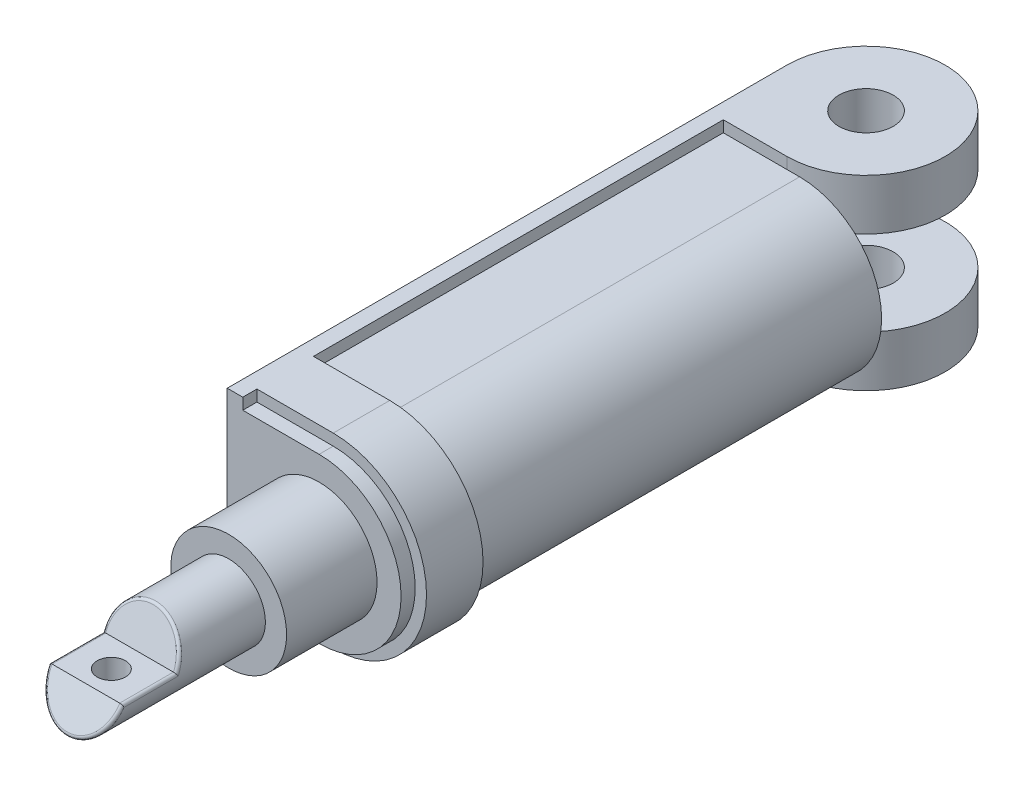
SolidWorks part; units mm, degrees
ref_plane "前视基准面" through (0, 0, 0) normal (0, 0, 1) x (1, 0, 0)
ref_plane "上视基准面" through (0, 0, 0) normal (0, 1, 0) x (1, 0, 0)
ref_plane "右视基准面" through (0, 0, 0) normal (1, 0, 0) x (0, 0, -1)
sketch "正视图" plane through (0, 0, 0) normal (0, 0, 1) x (1, 0, 0)
  line L0 (55.75, 273.25) -> (861.75, 273.25) construction
sketch "侧视图" plane through (0, 0, 0) normal (1, 0, 0) x (0, 0, -1)
  line L0 (-836.625, 271.75) -> (-66.625, 271.75) construction
sketch "上视图" plane through (0, 0, 0) normal (0, 1, 0) x (1, 0, 0)
  line L0 (71.77, 312.1) -> (815.77, 312.1) construction
ref_plane "基准面4" through (0, -30, 0) normal (0, 1, 0) x (1, 0, 0)
sketch "底视图" plane through (0, -30, 0) normal (0, 1, 0) x (1, 0, 0)
  line L0 (70.244, -367.6) -> (840.244, -367.6) construction
sketch "参考图" plane through (0, 0, 0) normal (0, 0, 1) x (1, 0, 0)
  line L0 (-599.619, 219.445) -> (198.381, 219.445) construction
  line L1 (199.5, 455.5) -> (997.5, 455.5) construction
  line L2 (-127.8038, 216.7504) -> (640.1962, 216.7504) construction
  line L3 (-679.1119, 349.8974) -> (-315.1119, 349.8974) construction
ref_plane "基准面5" through (0, -50.5, 0) normal (0, 1, 0) x (1, 0, 0)
sketch "草图1" plane through (0, -50.5, 0) normal (0, 1, 0) x (1, 0, 0)
  line L0 (65.375, 17.125) -> (65.375, 10.125)
  line L1 (65.375, 10.125) -> (58.375, 10.125)
  circle A0 centre (58.375, 17.125) radius 2.4
  circle A1 centre (58.375, 17.125) radius 7
  dimension "D3" = 4.8
  dimension "D4" = 14
  dimension "D1" = 17.125
  dimension "D2" = 58.375
extrude "凸台-拉伸1" add sketch "草图1" along normal blind 16.5 contours A1 A0 | A1 L1 L0 region at (63.1847, -50.5, -12.3153) region at (63.8114, -50.5, -11.6886)
sketch "草图2" plane through (0, 0, -10.125) normal (0, 0, 1) x (1, 0, 0)
  line L0 (73.5, -42.25) -> (57.25, -42.25) construction
  line L4 (65.375, -34) -> (65.375, -50.5) construction
  line L7 (73.5, -50.5) -> (57.25, -50.5)
  line L8 (73.5, -34) -> (57.25, -34)
  line L9 (70.75, -42.25) -> (57.25, -42.25) construction
  line L10 (70.75, -49.5) -> (57.25, -49.5)
  line L11 (70.75, -35) -> (57.25, -35)
  line L12 (60.775, -34) -> (55.975, -34) construction
  line L13 (65.375, -50.5) -> (58.375, -50.5) construction
  line L14 (65.375, -34) -> (65.375, -50.5)
  line L15 (64, -34) -> (64, -50.5)
  arc A4 (73.5, -50.5) -> (73.5, -34) centre (73.5, -42.25) ccw
  arc A5 (57.25, -34) -> (57.25, -50.5) centre (57.25, -42.25) ccw
  arc A6 (70.75, -49.5) -> (70.75, -35) centre (70.75, -42.25) ccw
  arc A7 (57.25, -35) -> (57.25, -49.5) centre (57.25, -42.25) ccw
  point P4 (65.375, -42.25)
  point P11 (64, -42.25)
  line M10 (65.375, -50.5) -> (65.375, -34)
  line M11 (65.375, -34) -> (58.375, -34)
  line M12 (58.375, -34) -> (58.375, -50.5)
  dimension "D1" = 16.25
  dimension "D2" = 1.375
  dimension "D3" = 14.5
extrude "凸台-拉伸2" add sketch "草图2" along normal blind 42.5 contours L11 A7 L10 M12 | L15 L11 L10 M12 | L15 L11 M11 M10 | L11 L15 L10 M10 | L10 L15 L7 M10 region at (64.6875, -50, -10.125) region at (64.6875, -42.25, -10.125) region at (64.6875, -34.5, -10.125) region at (61.1875, -42.25, -10.125) region at (54.7734, -42.25, -10.125)
sketch "草图3" plane through (0, 0, 32.375) normal (0, 0, 1) x (1, 0, 0)
  line L0 (64, -34) -> (64, -50.5) construction
  line L1 (65.375, -34) -> (65.375, -50.5) construction
  line L2 (57.25, -49.5) -> (70.75, -49.5)
  line L3 (70.75, -35) -> (57.25, -35)
  line L4 (57.25, -49.5) -> (70.75, -49.5)
  line L5 (70.75, -35) -> (57.25, -35)
  line L6 (57.25, -50.5) -> (73.5, -50.5)
  line L7 (73.5, -34) -> (57.25, -34)
  line L8 (57.25, -50.5) -> (73.5, -50.5)
  line L9 (73.5, -34) -> (57.25, -34)
  line L10 (64, -34) -> (64, -50.5)
  line L11 (65.375, -34) -> (65.375, -50.5)
  arc A2 (57.25, -35) -> (57.25, -49.5) centre (57.25, -42.25) ccw
  arc A3 (70.75, -49.5) -> (70.75, -35) centre (70.75, -42.25) ccw
  arc A4 (57.25, -35) -> (57.25, -49.5) centre (57.25, -42.25) ccw
  arc A5 (70.75, -49.5) -> (70.75, -35) centre (70.75, -42.25) ccw
  arc A6 (57.25, -34) -> (57.25, -50.5) centre (57.25, -42.25) ccw
  arc A7 (73.5, -50.5) -> (73.5, -34) centre (73.5, -42.25) ccw
  arc A8 (57.25, -34) -> (57.25, -50.5) centre (57.25, -42.25) ccw
  arc A9 (73.5, -50.5) -> (73.5, -34) centre (73.5, -42.25) ccw
  line M9 (64, -35) -> (57.25, -35)
  arc M10 (57.25, -35) -> (57.25, -49.5) centre (57.25, -42.25) ccw
  line M11 (57.25, -49.5) -> (64, -49.5)
  line M12 (64, -49.5) -> (64, -50.5)
  line M13 (64, -50.5) -> (65.375, -50.5)
  line M14 (65.375, -50.5) -> (65.375, -34)
  line M15 (65.375, -34) -> (64, -34)
  line M16 (64, -34) -> (64, -35)
  dimension "D1" = 0
  dimension "D2" = 0
extrude "凸台-拉伸3" add sketch "草图3" against normal blind 5 from offset 1.25 contours L9 A8 L8 M12 M11 M10 M9 M16 | L5 M14 M15 M16 | L4 M12 M13 M14 region at (60.625, -49.723, 32.375) region at (64.6875, -50, 32.375) region at (64.6875, -34.5, 32.375) offset against normal yes
ref_plane "基准面6" through (0, -42.25, 0) normal (0, 1, 0) x (1, 0, 0)
sketch "草图5" plane through (0, -42.25, 0) normal (0, 1, 0) x (1, 0, 0)
  line L1 (57.25, -32.375) -> (62.375, -32.375)
  line L2 (57.25, -32.375) -> (57.25, -40.375)
  line L3 (57.25, -40.375) -> (62.375, -40.375)
  line L4 (62.375, -32.375) -> (62.375, -40.375)
  line L5 (57.25, -40.375) -> (60.5, -40.375)
  line L6 (57.25, -40.375) -> (57.25, -54.875)
  line L7 (57.25, -54.875) -> (60.5, -54.875)
  line L8 (60.5, -40.375) -> (60.5, -54.875)
  dimension "D1" = 8
  dimension "D2" = 5.125
  dimension "D3" = 14.5
  dimension "D4" = 3.25
revolve "旋转1" add sketch "草图5" angle 360 about L2 region at (59.8125, -42.25, 36.375) region at (58.875, -42.25, 47.625)
sketch "草图6" plane through (0, 0, 0) normal (1, 0, 0) x (0, 0, -1)
  line L0 (-47, -39) -> (-48.25, -42.25)
  line L1 (-40.375, -39) -> (-54.875, -39) construction
  line L2 (-48.25, -42.25) -> (-53, -42.25)
  line L3 (-53, -42.25) -> (-54.875, -45.5)
  line L4 (-54.875, -45.5) -> (-54.875, -39)
  line L5 (-54.875, -39) -> (-54.875, -45.5) construction
  line L6 (-54.875, -39) -> (-47, -39)
  line L7 (-54.875, -42.25) -> (-53, -42.25)
  dimension "D1" = 1.875
  dimension "D2" = 4.75
  dimension "D3" = 1.25
extrude "切除-拉伸1" cut sketch "草图6" against normal through all both and the other way through all contours L4 L7 L2 L0 L6 | L7 L4 L3 region at (0, -40.5783, 51.241) region at (0, -43.3333, 54.25)
sketch "草图7" plane through (0, -42.25, 0) normal (0, 1, 0) x (1, 0, 0)
  line L0 (60.5, -48.25) -> (54, -48.25) construction
  line L1 (57.25, -48.25) -> (57.25, -50.75) construction
  circle A0 centre (57.25, -50.75) radius 1.25
  dimension "D2" = 2.5
  dimension "D1" = 2.5
extrude "切除-拉伸2" cut sketch "草图7" against normal through all and the other way through all
fillet "圆角1" radius 0.25 4 edges at (57.25, -45.5, 54.875) (54, -42.25, 50.625) (60.5, -42.25, 50.625) (57.25, -39, 47)
sketch "草图8" plane through (0, 0, 0) normal (1, 0, 0) x (0, 0, -1)
  line L0 (25.7912, -42.25) -> (24.125, -42.25)
  line L1 (10.125, -38.5) -> (25.7912, -38.5)
  line L2 (10.125, -38.5) -> (10.125, -46)
  line L3 (10.125, -46) -> (25.7912, -46)
  line L4 (25.7912, -38.5) -> (25.7912, -46)
  line L5 (24.125, -50.5) -> (24.125, -34) construction
  dimension "D1" = 10.125
  dimension "D2" = 7.5
extrude "切除-拉伸3" cut sketch "草图8" along normal through all both and the other way through all contours L4 L1 L2 L3 region at (0, -42.25, -17.9581)
sketch "草图9" plane through (65.375, 0, 0) normal (1, 0, 0) x (0, 0, -1)
  line L0 (-24.8742, -32.9163) -> (-35.7554, -51.9092)
  line L1 (-18.3542, -32.9163) -> (-29.2354, -51.9092)
  line L2 (-11.8342, -32.9163) -> (-22.7154, -51.9092)
  line L3 (-5.3142, -32.9163) -> (-16.1954, -51.9092)
  line L4 (1.2058, -32.9163) -> (-9.6754, -51.9092)
  line L5 (7.5775, -33.1752) -> (-3.1554, -51.9092)
  line L6 (7.5775, -44.5556) -> (3.3646, -51.9092)
  line L7 (7.5775, -52.2766) -> (7.5775, -33.1752)
  dimension "D1" = 7
split line "分割线1"
mirror "镜向2" about plane through (0, 0, 0) normal (1, 0, 0) of bodies 108
delete or keep bodies "实体-删除/保留 1" type delete bodies bodies 108
